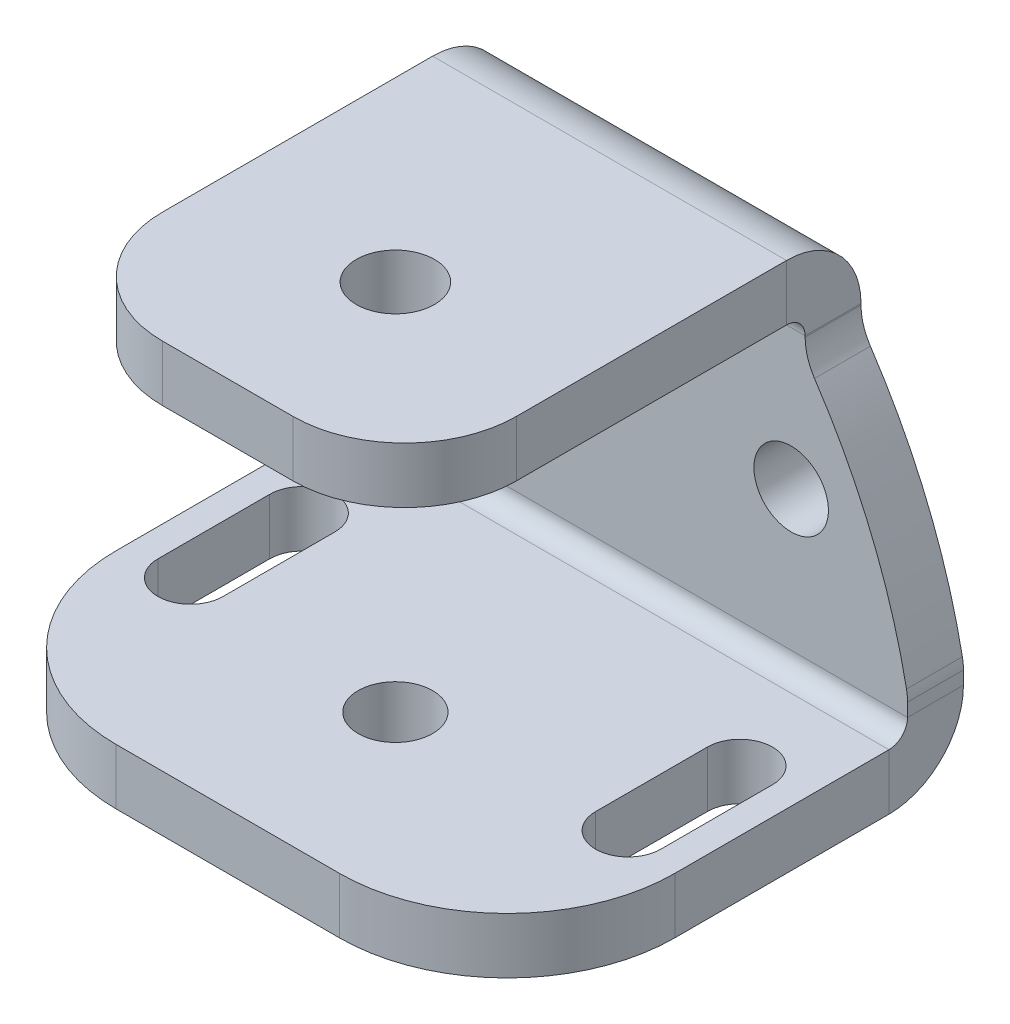
SolidWorks part; units mm, degrees
note: The reader was unsure of these and kept them because the rebuilt part matched: thickness of "Brida base1", "Brida de arista1", "Brida de arista2", "Chapa metálica4", "Chapa metálica5", "Chapa metálica6", "Chapa metálica7", "Chapa metálica8"; flange length of "Brida de arista1", "Brida de arista2".
material "aluminio"
ref_plane "Alzado" through (0, 0, 0) normal (0, 0, 1) x (1, 0, 0)
ref_plane "Planta" through (0, 0, 0) normal (0, 1, 0) x (1, 0, 0)
ref_plane "Vista lateral" through (0, 0, 0) normal (1, 0, 0) x (0, 0, -1)
sketch "Croquis1" plane through (0, 0, 0) normal (0, 0, 1) x (1, 0, 0)
  line L0 (0, 0) -> (30, 0)
  line L1 (30, 0) -> (24.5, 16) construction
  line L2 (24.5, 16) -> (5.5, 16)
  line L3 (5.5, 16) -> (0, 0) construction
  line L4 (15, 0) -> (15, 16) construction
  line L5 (-0.0459, 2.9428) -> (3.1942, 12.3684) construction
  line L6 (25.3834, 16.5063) -> (31.1519, -0.2748) construction
  line L7 (5.5, 16) -> (5.5, 15)
  line L8 (0, 0) -> (0, 2)
  line L9 (24.5, 16) -> (24.5, 15)
  line L10 (30, 0) -> (30, 2)
  arc A0 (24.5, 15) -> (30, 2) centre (-2.5787, -4.1198) cw
  arc A2 (0, 2) -> (5.5, 15) centre (32.5787, -4.1198) cw
  dimension "D6" = 2
  dimension "D1" = 30
  dimension "D2" = 16
  dimension "D3" = 19
  dimension "D4" = 1
  dimension "D5" = 1
  dimension "D7" = 1
  dimension "D8" = 2
  dimension "D9" = 1
base flange "Brida base1" sketch "Croquis1" thickness 3 reverse thickness direction no parameters "D1"=0.7366
edge flange "Brida de arista1" sketch "Croquis8" flange angle 90 flange length 21.5 flange position material outside bend radius 1 thickness 3 relief rectangular parameters "D6"=10
sketch "Croquis8" plane through (0, 0, 0) normal (0, -1, 0) x (1, 0, 0)
  line L0 (0, 0) -> (30, 0) construction
  line L1 (0, 0) -> (30, 0)
  line L2 (0, 0) -> (0, 21.5)
  line L3 (0, 21.5) -> (30, 21.5)
  line L4 (30, 21.5) -> (30, 0)
  line L5 (0, -3) -> (30, -3) construction
  dimension "D1" = 24.5
bend "Pliegue de arista5" bend radius 1 bend angle 90 parameters "D5"=1
edge flange "Brida de arista2" sketch "Croquis11" flange angle 90 flange length 21.5 flange position bend outside bend radius 1 thickness 3 relief rectangular parameters "D6"=10
sketch "Croquis11" plane through (0, 16, 0) normal (0, 1, 0) x (-1, 0, 0)
  line L0 (-24.5, 0) -> (-5.5, 0) construction
  line L1 (-24.5, 0) -> (-5.5, 0)
  line L2 (-24.5, 0) -> (-24.5, 21.5)
  line L4 (-5.5, 21.5) -> (-5.5, 0)
  line L5 (-5.5, 21.5) -> (-24.5, 21.5)
  line L6 (-30, 21.5) -> (0, 21.5) construction
bend "Pliegue de arista2" bend radius 1 bend angle 90 parameters "D5"=2
sketch "Croquis12" plane through (0, -3, 0) normal (0, 1, 0) x (1, 0, 0)
  line L0 (15, -21.5) -> (15, 3) construction
  line L1 (5.5, -21.5) -> (24.5, -21.5) construction
  line L2 (24.5, 3) -> (5.5, 3) construction
  circle A0 centre (15, -12.5) radius 2
  dimension "D1" = 4
  dimension "D2" = 15.5
extrude "Cortar-Extruir1" cut sketch "Croquis12" along normal up to next normal cut yes
sketch "Croquis13" plane through (0, 0, 0) normal (0, 1, 0) x (1, 0, 0)
  line L0 (15, -1) -> (15, -21.5) construction
  line L1 (24.5, -1) -> (5.5, -1) construction
  line L2 (15, -11.25) -> (9.8308, -11.25) construction
  line L3 (3.25, -5.75) -> (3.25, -11.75) construction
  line L4 (5, -5.75) -> (5, -11.75)
  line L5 (1.5, -5.75) -> (1.5, -11.75)
  line L6 (30, -21.5) -> (0, -21.5) construction
  line L8 (26.75, -5.75) -> (26.75, -11.75) construction
  line L9 (25, -5.75) -> (25, -11.75)
  line L10 (28.5, -5.75) -> (28.5, -11.75)
  arc A0 (5, -5.75) -> (1.5, -5.75) centre (3.25, -5.75) ccw
  arc A1 (1.5, -11.75) -> (5, -11.75) centre (3.25, -11.75) ccw
  arc A2 (25, -5.75) -> (28.5, -5.75) centre (26.75, -5.75) cw
  arc A3 (28.5, -11.75) -> (25, -11.75) centre (26.75, -11.75) cw
  circle A4 centre (15, -12.5) radius 2 construction
  point P8 (3.25, -8.75)
  point P17 (26.75, -8.75)
  dimension "D2" = 1.75
  dimension "D4" = 0.75
  dimension "D1" = 6
  dimension "D3" = 11.75
extrude "Cortar-Extruir2" cut sketch "Croquis13" against normal up to next normal cut yes
sketch "Croquis26" plane through (0, 0, -3) normal (0, 0, -1) x (-1, 0, 0)
  line L0 (-15, 16) -> (-15, 1) construction
  line L1 (-24.5, 16) -> (-5.5, 16) construction
  line L2 (-6.25, 8.5) -> (-15, 8.5) construction
  line L3 (-30, 1) -> (0, 1) construction
  circle A1 centre (-6.25, 8.5) radius 2
  circle A2 centre (-23.75, 8.5) radius 2
  dimension "D1" = 4
  dimension "D2" = 8.75
extrude "Cortar-Extruir6" cut sketch "Croquis26" against normal up to next normal cut yes
hole_wizard "Taladro roscado M51" positions "Croquis3D1" profile "Croquis22" tap size "M5" standard "Iso" end condition up to next
sketch3d "Croquis3D1"
  circle A0 centre (15, 0, 12.5) radius 2 construction
  point P5 (15, 20, 12.5)
  point P11 (15, 2, 12.5)
sketch "Croquis22" plane through (15, 20, 12.5) normal (1, 0, 0) x (0, 0, 1)
  line L0 (0, 0) -> (0, 3)
  line L1 (0, 3) -> (2.1, 3)
  line L2 (2.1, 3) -> (2.1, 0)
  line L5 (2.1, 0) -> (0, 0)
  line L11 (0, -6.35) -> (0, 107.95) construction
  dimension "Diámetro de perforador para roscar hasta el siguiente" = 4.2
  dimension "Profundidad de perforador para roscar hasta el siguiente" = 3
cosmetic thread "Rosca de taladro2"
fillet "Redondeo2" radius 9 2 edges at (30, -1.5, 21.5) (0, -1.5, 21.5)
fillet "Redondeo3" radius 6 2 edges at (24.5, 18.5, 21.5) (5.5, 18.5, 21.5)
fillet "Redondeo4" radius 3 4 edges at (30, 2, -1.5) (0, 2, -1.5) (5.5, 15, -1.5) (24.5, 15, -1.5)
sketch "Líneas de pliegue1" [suppressed] plane through (0, 0, 0) normal (0, 1, 0) x (1, 0, 0)
sketch "Cuadro delimitador1" [suppressed] plane through (0, 0, 0) normal (0, 1, 0) x (1, 0, 0)
sheet metal parameters "Chapa metálica4" thickness 3 parameters "D1"=0.7366
flat pattern "Chapa desplegada4" [suppressed]
sketch "Líneas de pliegue2" plane through (0, 0, 0) normal (0, 1, 0) x (1, 0, 0)
sketch "Cuadro delimitador2" [suppressed] plane through (0, 0, 0) normal (0, 1, 0) x (1, 0, 0)
sheet metal parameters "Chapa metálica5" thickness 3 parameters "D1"=0.7366, "D7"=2
flat pattern "Chapa desplegada4" [suppressed]
sketch "Líneas de pliegue2" plane through (0, 0, 0) normal (0, 1, 0) x (1, 0, 0)
sketch "Cuadro delimitador2" [suppressed] plane through (0, 0, 0) normal (0, 1, 0) x (1, 0, 0)
bend of the flat pattern "Aplanar-<Pliegue de arista5>1"
sheet metal parameters "Chapa metálica6" thickness 3 parameters "D1"=0.7366, "D7"=2
flat pattern "Chapa desplegada4" [suppressed]
sketch "Líneas de pliegue2" plane through (0, 0, 0) normal (0, 1, 0) x (1, 0, 0)
sketch "Cuadro delimitador2" [suppressed] plane through (0, 0, 0) normal (0, 1, 0) x (1, 0, 0)
bend of the flat pattern "Aplanar-<Pliegue de arista2>1"
bend of the flat pattern "Aplanar-<Pliegue de arista5>2"
sheet metal parameters "Chapa metálica7" thickness 3 parameters "D1"=0.7366, "D7"=2
flat pattern "Chapa desplegada4" [suppressed]
sketch "Líneas de pliegue2" plane through (0, 0, 0) normal (0, 1, 0) x (1, 0, 0)
sketch "Cuadro delimitador2" [suppressed] plane through (0, 0, 0) normal (0, 1, 0) x (1, 0, 0)
bend of the flat pattern "Aplanar-<Pliegue de arista2>1"
bend of the flat pattern "Aplanar-<Pliegue de arista5>3"
sheet metal parameters "Chapa metálica8" thickness 3 parameters "D1"=0.7366, "D7"=2
flat pattern "Chapa desplegada4" [suppressed]
sketch "Líneas de pliegue2" plane through (0, 0, 0) normal (0, 1, 0) x (1, 0, 0)
sketch "Cuadro delimitador2" [suppressed] plane through (0, 0, 0) normal (0, 1, 0) x (1, 0, 0)
bend of the flat pattern "Aplanar-<Pliegue de arista2>1"
bend of the flat pattern "Aplanar-<Pliegue de arista5>4"
sheet metal parameters "Chapa metálica15" thickness 2 parameters "D1"=0.7366
flat pattern "Chapa desplegada4" [suppressed]
sketch "Líneas de pliegue3" plane through (0, 0, 0) normal (0, 0, 1) x (1, 0, 0)
  line L0 (22.5, 21.4635) -> (7.5, 21.4635) construction
  line L1 (0.1923, -0.9635) -> (29.8077, -0.9635) construction
  line L2 (22.5, 21.4635) -> (7.5, 21.4635) construction
  line L3 (0.1923, -0.9635) -> (29.8077, -0.9635) construction
sketch3d "Cuadro delimitador3" [suppressed]
  line L0 (30, -24.927, 0) -> (30, 46.177, 0) construction
  line L1 (0, -24.927, 0) -> (0, 46.177, 0) construction
  line L2 (30, -24.927, 0) -> (0, -24.927, 0) construction
  line L3 (30, 46.177, 0) -> (0, 46.177, 0) construction
bend of the flat pattern "Aplanar-<Pliegue de arista2>3"
bend of the flat pattern "Aplanar-<Pliegue de arista5>7"
sheet metal parameters "Chapa metálica17" thickness 2 parameters "D1"=0.7366
flat pattern "Chapa desplegada4" [suppressed]
sketch "Líneas de pliegue3" plane through (0, 0, 0) normal (0, 1, 0) x (1, 0, 0)
sketch "Cuadro delimitador3" [suppressed] plane through (0, 0, 0) normal (0, 1, 0) x (1, 0, 0)
bend of the flat pattern "Aplanar-<Pliegue de arista2>2"
bend of the flat pattern "Aplanar-<Pliegue de arista5>6"
